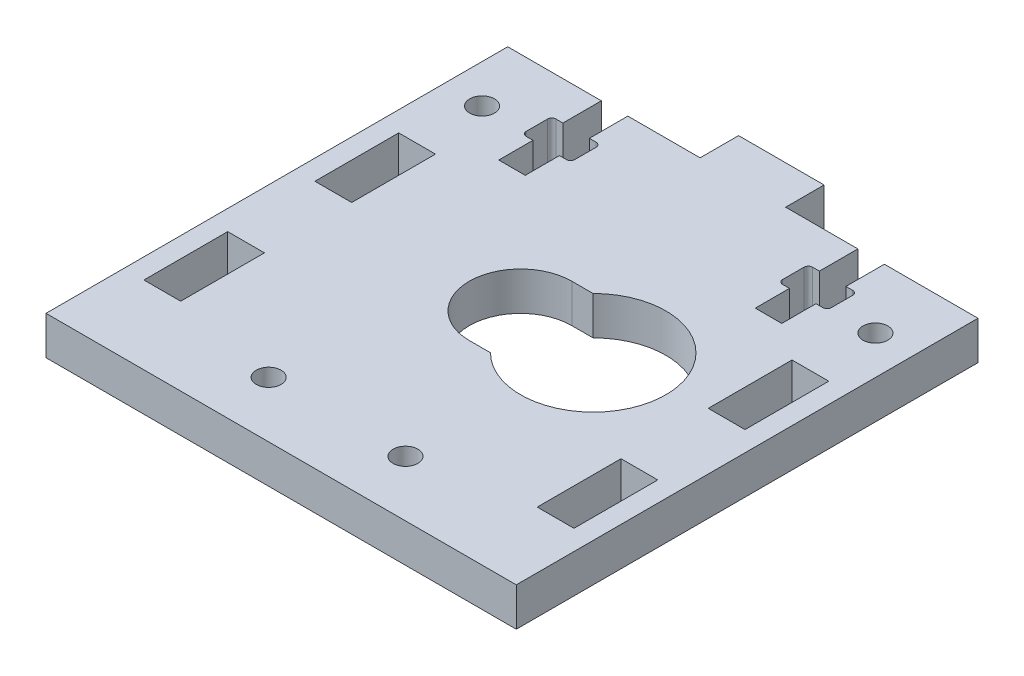
SolidWorks part; units mm, degrees
ref_plane "Front Plane" through (0, 0, 0) normal (0, 0, 1) x (1, 0, 0)
ref_plane "Top Plane" through (0, 0, 0) normal (0, 1, 0) x (1, 0, 0)
ref_plane "Right Plane" through (0, 0, 0) normal (1, 0, 0) x (0, 0, -1)
sketch "Sketch1" plane through (0, 0, 0) normal (0, 1, 0) x (1, 0, 0)
  line L1 (-27.5, 27) -> (27.5, 27)
  line L2 (-27.5, 27) -> (-27.5, -27)
  line L3 (-27.5, -27) -> (27.5, -27)
  line L4 (27.5, 27) -> (27.5, -27)
  line L5 (-27.5, 27) -> (27.5, -27) construction
  line L6 (-27.5, -27) -> (27.5, 27) construction
  point P0 (0, 0)
  dimension "D1" = 55
  dimension "D2" = 54
extrude "MainShape" add sketch "Sketch1" along normal blind 4.5
sketch "Sketch2" plane through (0, 4.5, 0) normal (0, 1, 0) x (1, 0, 0)
  line L0 (0, -27) -> (0, 27) construction
  line L1 (-27.5, -27) -> (27.5, -27) construction
  line L2 (27.5, 27) -> (-27.5, 27) construction
  line L4 (-5, 31.5) -> (5, 31.5)
  line L5 (-5, 31.5) -> (-5, 22.5)
  line L6 (-5, 22.5) -> (5, 22.5)
  line L7 (5, 31.5) -> (5, 22.5)
  line L8 (-5, 31.5) -> (5, 22.5) construction
  line L9 (-5, 22.5) -> (5, 31.5) construction
  dimension "D1" = 10
  dimension "D2" = 4.5
extrude "Tab1" add sketch "Sketch2" against normal through all
sketch "Sketch4" plane through (0, 4.5, 0) normal (0, 1, 0) x (1, 0, 0)
  line L0 (0, 31.5) -> (0, -27) construction
  line L1 (5, 31.5) -> (-5, 31.5) construction
  line L2 (-27.5, -27) -> (27.5, -27) construction
  line L3 (-15, 27) -> (-15, 15) construction
  line L4 (-5, 27) -> (-27.5, 27) construction
  line L5 (-13.45, 15) -> (-16.55, 15) construction
  line L6 (-16.55, 15) -> (-16.55, 27) construction
  line L7 (-13.45, 15) -> (-16.55, 15)
  line L8 (-16.55, 15) -> (-16.55, 19)
  line L9 (-16.55, 19) -> (-17.35, 19)
  line L10 (-17.85, 19.5) -> (-17.85, 22)
  line L11 (-17.35, 22.5) -> (-16.55, 22.5)
  line L12 (-16.55, 22.5) -> (-16.55, 27)
  line L13 (-16.55, 27) -> (-13.45, 27)
  line L14 (-13.45, 15) -> (-13.45, 27) construction
  line L15 (-13.45, 22.5) -> (-13.45, 27)
  line L16 (-12.65, 22.5) -> (-13.45, 22.5)
  line L17 (-12.15, 19.5) -> (-12.15, 22)
  line L18 (-13.45, 19) -> (-12.65, 19)
  line L19 (-13.45, 15) -> (-13.45, 19)
  line L20 (13.45, 15) -> (13.45, 27) construction
  line L21 (16.55, 15) -> (16.55, 27) construction
  line L22 (13.45, 15) -> (16.55, 15) construction
  line L23 (15, 27) -> (15, 15) construction
  line L24 (13.45, 15) -> (13.45, 19)
  line L25 (13.45, 19) -> (12.65, 19)
  line L26 (12.15, 19.5) -> (12.15, 22)
  line L27 (12.65, 22.5) -> (13.45, 22.5)
  line L28 (13.45, 22.5) -> (13.45, 27)
  line L29 (16.55, 27) -> (13.45, 27)
  line L30 (16.55, 22.5) -> (16.55, 27)
  line L31 (17.35, 22.5) -> (16.55, 22.5)
  line L32 (17.85, 19.5) -> (17.85, 22)
  line L33 (16.55, 19) -> (17.35, 19)
  line L34 (16.55, 15) -> (16.55, 19)
  line L35 (13.45, 15) -> (16.55, 15)
  arc A0 (-17.35, 19) -> (-17.85, 19.5) centre (-17.35, 19.5) cw
  arc A1 (-12.15, 19.5) -> (-12.65, 19) centre (-12.65, 19.5) cw
  arc A2 (-12.65, 22.5) -> (-12.15, 22) centre (-12.65, 22) cw
  arc A3 (-17.85, 22) -> (-17.35, 22.5) centre (-17.35, 22) cw
  arc A4 (17.85, 22) -> (17.35, 22.5) centre (17.35, 22) ccw
  arc A5 (12.65, 22.5) -> (12.15, 22) centre (12.65, 22) ccw
  arc A6 (12.15, 19.5) -> (12.65, 19) centre (12.65, 19.5) ccw
  arc A7 (17.35, 19) -> (17.85, 19.5) centre (17.35, 19.5) ccw
  point P24 (-17.85, 19)
  point P27 (-12.15, 19)
  point P30 (-12.15, 22.5)
  point P33 (-17.85, 22.5)
  point P56 (17.85, 22.5)
  point P57 (12.15, 22.5)
  point P58 (12.15, 19)
  point P59 (17.85, 19)
  dimension "D7" = 0.5
  dimension "D1" = 12
  dimension "D2" = 1.55
  dimension "D3" = 3.5
  dimension "D4" = 2.85
  dimension "D5" = 8
  dimension "D6" = 15
extrude "Cut-Extrude2" cut sketch "Sketch4" against normal through all
sketch "Sketch5" plane through (0, 4.5, 0) normal (0, 1, 0) x (1, 0, 0)
  line L0 (0, -27) -> (0, 31.5) construction
  line L1 (-27.5, -27) -> (27.5, -27) construction
  line L2 (5, 31.5) -> (-5, 31.5) construction
  line L3 (23, 27) -> (23, -27) construction
  line L4 (27.5, 27) -> (16.55, 27) construction
  line L5 (-23, 27) -> (-23, -27) construction
  line L6 (20.85, 11.9) -> (25.15, 11.9)
  line L7 (20.85, 11.9) -> (20.85, 2.1)
  line L8 (20.85, 2.1) -> (25.15, 2.1)
  line L9 (25.15, 11.9) -> (25.15, 2.1)
  line L10 (20.85, 11.9) -> (25.15, 2.1) construction
  line L11 (20.85, 2.1) -> (25.15, 11.9) construction
  line L12 (-20.85, 2.1) -> (-25.15, 11.9) construction
  line L13 (-20.85, 11.9) -> (-25.15, 2.1) construction
  line L14 (-25.15, 11.9) -> (-25.15, 2.1)
  line L15 (-20.85, 2.1) -> (-25.15, 2.1)
  line L16 (-20.85, 11.9) -> (-20.85, 2.1)
  line L17 (-20.85, 11.9) -> (-25.15, 11.9)
  line L18 (-27.5, -3) -> (27.5, -3) construction
  line L19 (-27.5, 27) -> (-27.5, -27) construction
  line L20 (27.5, -27) -> (27.5, 27) construction
  line L21 (-20.85, -17.9) -> (-25.15, -8.1) construction
  line L22 (-20.85, -8.1) -> (-25.15, -17.9) construction
  line L23 (20.85, -8.1) -> (25.15, -17.9) construction
  line L24 (20.85, -17.9) -> (25.15, -8.1) construction
  line L25 (-20.85, -17.9) -> (-25.15, -17.9)
  line L26 (-20.85, -17.9) -> (-20.85, -8.1)
  line L27 (-20.85, -8.1) -> (-25.15, -8.1)
  line L28 (-25.15, -17.9) -> (-25.15, -8.1)
  line L29 (25.15, -17.9) -> (25.15, -8.1)
  line L30 (20.85, -8.1) -> (25.15, -8.1)
  line L31 (20.85, -17.9) -> (20.85, -8.1)
  line L32 (20.85, -17.9) -> (25.15, -17.9)
  line L33 (-20.85, 11.9) -> (-25.15, 2.1) construction
  point P10 (23, 7)
  point P21 (-23, 7)
  point P36 (-23, -13)
  point P37 (23, -13)
  dimension "D1" = 23
  dimension "D2" = 9.8
  dimension "D3" = 4.3
  dimension "D4" = 20
  dimension "D5" = 20
extrude "Cut-Extrude3" cut sketch "Sketch5" against normal through all
sketch "Sketch6" plane through (0, 4.5, 0) normal (0, 1, 0) x (1, 0, 0)
  line L0 (0, -27) -> (0, 27) construction
  line L1 (5, 31.5) -> (-5, 31.5) construction
  line L3 (-27.5, 1) -> (27.5, 1) construction
  line L4 (-27.5, 27) -> (-27.5, -27) construction
  line L5 (27.5, -27) -> (27.5, 27) construction
  line L6 (27.5, 27) -> (16.55, 27) construction
  line L7 (-27.5, -27) -> (27.5, -27) construction
  line L9 (-27.5, 27) -> (27.5, 27) construction
  circle A0 centre (0, 1) radius 12
  point P4 (0, 31.5)
  dimension "D1" = 24
  dimension "D2" = 26
extrude "Cut-Extrude4" cut sketch "Sketch6" against normal through all
sketch "Sketch7" plane through (0, 4.5, 0) normal (0, 1, 0) x (1, 0, 0)
  line L0 (0, 1) -> (0, -27) construction
  line L3 (-27.5, -27) -> (27.5, -27) construction
  line L4 (8, -20.46) -> (-8, -20.46) construction
  circle A1 centre (-8, -20.46) radius 1.45
  circle A2 centre (8, -20.46) radius 1.45
  point P8 (0, -20.46)
  dimension "D1" = 2.9
  dimension "D3" = 21.46
extrude "Cut-Extrude5" [suppressed] cut sketch "Sketch7" against normal through all
sketch "Sketch8" plane through (0, 4.5, 0) normal (0, 1, 0) x (1, 0, 0)
  line L0 (-12, 1) -> (12, 1) construction
  line L1 (0, 1) -> (0, -20.46) construction
  line L2 (8, -20.46) -> (-8, -20.46) construction
  line L3 (0, -11) -> (0, 13) construction
  circle A0 centre (-8, -20.46) radius 1.45
  circle A1 centre (0, 1) radius 12 construction
  circle A2 centre (8, -20.46) radius 1.45
  dimension "D3" = 2.9
  dimension "D1" = 90
  dimension "D4" = 21.46
extrude "Cut-Extrude6" cut sketch "Sketch8" against normal through all
sketch "Sketch9" plane through (0, 4.5, 0) normal (0, 1, 0) x (1, 0, 0)
  line L0 (0, -27) -> (0, 31.5) construction
  line L1 (-27.5, -27) -> (27.5, -27) construction
  line L2 (5, 31.5) -> (-5, 31.5) construction
  line L3 (16, -27) -> (16, -16) construction
  line L4 (14.45, -16) -> (17.55, -16) construction
  line L5 (17.55, -16) -> (17.55, -27) construction
  line L6 (17.55, -27) -> (17.55, -22.5)
  line L7 (17.55, -22.5) -> (18.35, -22.5)
  line L8 (18.85, -22) -> (18.85, -19.5)
  line L9 (18.35, -19) -> (17.55, -19)
  line L10 (17.55, -19) -> (17.55, -16)
  line L11 (17.55, -16) -> (14.45, -16)
  line L12 (17.55, -27) -> (14.45, -27)
  line L13 (14.45, -16) -> (14.45, -27) construction
  line L14 (14.45, -19) -> (14.45, -16)
  line L15 (13.65, -19) -> (14.45, -19)
  line L16 (13.15, -22) -> (13.15, -19.5)
  line L17 (14.45, -22.5) -> (13.65, -22.5)
  line L18 (14.45, -27) -> (14.45, -22.5)
  line L19 (-14.45, -16) -> (-14.45, -27) construction
  line L20 (-17.55, -16) -> (-17.55, -27) construction
  line L21 (-14.45, -16) -> (-17.55, -16) construction
  line L22 (-16, -27) -> (-16, -16) construction
  line L23 (-14.45, -27) -> (-14.45, -22.5)
  line L24 (-14.45, -22.5) -> (-13.65, -22.5)
  line L25 (-13.15, -22) -> (-13.15, -19.5)
  line L26 (-13.65, -19) -> (-14.45, -19)
  line L27 (-14.45, -19) -> (-14.45, -16)
  line L28 (-17.55, -27) -> (-14.45, -27)
  line L29 (-17.55, -16) -> (-14.45, -16)
  line L30 (-17.55, -19) -> (-17.55, -16)
  line L31 (-18.35, -19) -> (-17.55, -19)
  line L32 (-18.85, -22) -> (-18.85, -19.5)
  line L33 (-17.55, -22.5) -> (-18.35, -22.5)
  line L34 (-17.55, -27) -> (-17.55, -22.5)
  arc A0 (18.35, -22.5) -> (18.85, -22) centre (18.35, -22) ccw
  arc A1 (18.85, -19.5) -> (18.35, -19) centre (18.35, -19.5) ccw
  arc A2 (13.15, -19.5) -> (13.65, -19) centre (13.65, -19.5) cw
  arc A3 (13.65, -22.5) -> (13.15, -22) centre (13.65, -22) cw
  arc A4 (-13.65, -22.5) -> (-13.15, -22) centre (-13.65, -22) ccw
  arc A5 (-13.15, -19.5) -> (-13.65, -19) centre (-13.65, -19.5) ccw
  arc A6 (-18.85, -19.5) -> (-18.35, -19) centre (-18.35, -19.5) cw
  arc A7 (-18.35, -22.5) -> (-18.85, -22) centre (-18.35, -22) cw
  point P16 (18.85, -22.5)
  point P19 (18.85, -19)
  point P30 (13.15, -19)
  point P31 (13.15, -22.5)
  point P54 (-13.15, -22.5)
  point P55 (-13.15, -19)
  point P56 (-18.85, -19)
  point P57 (-18.85, -22.5)
  dimension "D7" = 0.5
  dimension "D2" = 1.55
  dimension "D1" = 11
  dimension "D3" = 8
  dimension "D4" = 3.5
  dimension "D5" = 2.85
  dimension "D6" = 16
extrude "Cut-Extrude7" [suppressed] cut sketch "Sketch9" against normal through all
sketch "Sketch10" [suppressed] plane through (0, 0, 27) normal (0, 0, 1) x (1, 0, 0)
  line L0 (-27.5, 2.25) -> (27.5, 2.25) construction
  line L1 (-27.5, 4.5) -> (-27.5, 0) construction
  line L2 (27.5, 4.5) -> (27.5, 0) construction
  line L3 (-16, 4.5) -> (-16, 0) construction
  line L4 (-14.25, 4.5) -> (-17.75, 4.5) construction
  line L5 (16, 4.5) -> (16, 0) construction
  line L6 (17.75, 4.5) -> (14.25, 4.5) construction
  line L7 (17.75, 0) -> (14.25, 0) construction
  line L8 (-14.25, 0) -> (-17.75, 0) construction
  circle A0 centre (-16, 2.25) radius 1.6
  circle A1 centre (16, 2.25) radius 1.6
  dimension "D1" = 3.2
  dimension "D2" = 3.2
sketch "Sketch11" plane through (0, 4.5, 0) normal (0, 1, 0) x (1, 0, 0)
  line L0 (-20.85, 7) -> (-25.15, 7) construction
  line L1 (-20.85, 2.1) -> (-20.85, 11.9) construction
  line L2 (-25.15, 11.9) -> (-25.15, 2.1) construction
  line L3 (-23, 7) -> (-23, 27) construction
  line L4 (-16.55, 27) -> (-27.5, 27) construction
  line L5 (0, 31.5) -> (0, 0) construction
  line L6 (5, 31.5) -> (-5, 31.5) construction
  line L7 (23, 7) -> (23, 27) construction
  line L8 (20.85, 7) -> (25.15, 7) construction
  line L9 (-23, 7) -> (-23, 27) construction
  circle A0 centre (-23, 19.5) radius 1.45
  circle A1 centre (23, 19.5) radius 1.45
  dimension "D1" = 2.9
  dimension "D2" = 7.5
extrude "Cut-Extrude8" cut sketch "Sketch11" against normal through all
sketch "Sketch12" [suppressed] plane through (0, 4.5, 0) normal (0, 1, 0) x (1, 0, 0)
  line L0 (-27.5, -7) -> (-34, -17)
  line L1 (-27.5, 27) -> (-27.5, -27) construction
  line L2 (-34, -17) -> (-34, -27)
  line L3 (-34, -27) -> (-27.5, -27)
  line L4 (-27.5, -27) -> (-27.5, -7)
  line L5 (-27.5, -27) -> (27.5, -27) construction
  line L6 (0, -27) -> (0, 31.5) construction
  line L7 (5, 31.5) -> (-5, 31.5) construction
  line L8 (27.5, -27) -> (27.5, -7)
  line L9 (34, -27) -> (27.5, -27)
  line L10 (34, -17) -> (34, -27)
  line L11 (27.5, -7) -> (34, -17)
  point P4 (0, -27)
  dimension "D1" = 34
  dimension "D2" = 10
  dimension "D3" = 20
extrude "Boss-Extrude1" [suppressed] add sketch "Sketch12" against normal through all
sketch "Sketch14" [suppressed] plane through (0, 4.5, 0) normal (0, 1, 0) x (1, 0, 0)
  line L0 (-34, -27) -> (34, -27) construction
  line L2 (-34, -27) -> (34, -27) construction
  line L3 (0, -27) -> (0, 31.5) construction
  line L4 (5, 31.5) -> (-5, 31.5) construction
  line L6 (26.25, -16.5) -> (26.25, -27) construction
  line L8 (-28, -27) -> (-28, -16.5) construction
  line L9 (-26.25, -16.5) -> (-29.75, -16.5) construction
  line L10 (-29.75, -16.5) -> (-29.75, -27) construction
  line L11 (-26.25, -27) -> (-29.75, -27)
  line L12 (-29.75, -27) -> (-29.75, -23.2)
  line L13 (-29.75, -23.2) -> (-30.75, -23.2)
  line L14 (-31, -22.95) -> (-31, -19.25)
  line L15 (-30.75, -19) -> (-29.75, -19)
  line L16 (-29.75, -19) -> (-29.75, -16.5)
  line L17 (-29.75, -16.5) -> (-26.25, -16.5)
  line L18 (-26.25, -16.5) -> (-26.25, -27) construction
  line L19 (-26.25, -19) -> (-26.25, -16.5)
  line L20 (-25.25, -19) -> (-26.25, -19)
  line L21 (-25, -22.95) -> (-25, -19.25)
  line L22 (-26.25, -23.2) -> (-25.25, -23.2)
  line L23 (-26.25, -27) -> (-26.25, -23.2)
  line L24 (29.75, -16.5) -> (29.75, -27) construction
  line L25 (26.25, -16.5) -> (29.75, -16.5) construction
  line L26 (28, -27) -> (28, -16.5) construction
  line L27 (26.25, -27) -> (26.25, -23.2)
  line L28 (26.25, -23.2) -> (25.25, -23.2)
  line L29 (25, -22.95) -> (25, -19.25)
  line L30 (25.25, -19) -> (26.25, -19)
  line L31 (26.25, -19) -> (26.25, -16.5)
  line L32 (29.75, -16.5) -> (26.25, -16.5)
  line L33 (29.75, -19) -> (29.75, -16.5)
  line L34 (30.75, -19) -> (29.75, -19)
  line L35 (31, -22.95) -> (31, -19.25)
  line L36 (29.75, -23.2) -> (30.75, -23.2)
  line L37 (29.75, -27) -> (29.75, -23.2)
  line L38 (26.25, -27) -> (29.75, -27)
  line L39 (-26.25, -16.5) -> (-26.25, -27) construction
  arc A0 (-30.75, -23.2) -> (-31, -22.95) centre (-30.75, -22.95) cw
  arc A1 (-31, -19.25) -> (-30.75, -19) centre (-30.75, -19.25) cw
  arc A2 (-25, -19.25) -> (-25.25, -19) centre (-25.25, -19.25) ccw
  arc A3 (-25.25, -23.2) -> (-25, -22.95) centre (-25.25, -22.95) ccw
  arc A4 (25.25, -23.2) -> (25, -22.95) centre (25.25, -22.95) cw
  arc A5 (25, -19.25) -> (25.25, -19) centre (25.25, -19.25) cw
  arc A6 (31, -19.25) -> (30.75, -19) centre (30.75, -19.25) ccw
  arc A7 (30.75, -23.2) -> (31, -22.95) centre (30.75, -22.95) ccw
  point P2 (0, -27)
  dimension "D10" = 0.5
  dimension "D4" = 1.55
  dimension "D6" = 11
  dimension "D2" = 28
  dimension "D3" = 2.85
  dimension "D5" = 3.5
  dimension "D7" = 8
extrude "Cut-Extrude9" [suppressed] cut sketch "Sketch14" against normal through all
sketch "Sketch15" plane through (0, 4.5, 0) normal (0, 1, 0) x (1, 0, 0)
  circle A0 centre (0, 1) radius 12
  circle A1 centre (0, 1) radius 6
  circle A2 centre (0, 1) radius 12 construction
  dimension "D1" = 12
extrude "Boss-Extrude2" add sketch "Sketch15" against normal through all
sketch "Sketch16" plane through (0, 4.5, 0) normal (0, 1, 0) x (1, 0, 0)
  line L0 (0, 1) -> (27.5, 1) construction
  line L1 (27.5, -27) -> (27.5, 27) construction
  line L2 (0, 7) -> (2.4792, 7)
  line L3 (0, -5) -> (2.4792, -5)
  line L4 (0, 7) -> (0, -5)
  arc A0 (2.4792, -5) -> (2.4792, 7) centre (8.5, 1) ccw
  circle A1 centre (0, 1) radius 6 construction
  dimension "D1" = 17
  dimension "D2" = 8.5
extrude "Cut-Extrude10" cut sketch "Sketch16" against normal through all
equation "\"X-ROD-SPACING\"=45"
equation "\"Y-ROD-SPACING\"=75"
equation "\"Z-ROD-SPACING\"=17.5"
equation "\"Y-BED-OFFSET\"=2"
equation "\"Y-BED-ROD-INSET\"=3.5"
equation "\"Y-BED-SCREW-SPACING\"=209"
equation "\"Y-BED-SCREW-CUTOUT-SLOT-HEIGHT\"=2"
equation "\"T-SLOT-NUT-FILLET-RADIUS\"=0.5"
equation "\"T-SLOT-SCREW-SHAFT-RADIUS\"=1.55"
equation "\"T-SLOT-SCREW-SHAFT-CUTOUT-LENGTH\"=11.0"
equation "\"T-SLOT-NUT-DEPTH\"=3.5"
equation "\"T-SLOT-NUT-WIDTH\"=2.85"
equation "\"T-SLOT-NUT-END-DISTANCE\"=8"
equation "\"ACRYLIC-THICKNESS\"=10"
equation "\"ACRYLIC-THICKNESS2\"=4.5"
equation "\"ACRYLIC-TAB-CUTOUT-SIZE\"=\"ACRYLIC-THICKNESS\"+\"ACRYLIC-TAB-TOLERANCE\"*2"
equation "\"ACRYLIC-TAB-WIDTH\"=\"ACRYLIC-THICKNESS\""
equation "\"ACRYLIC-M3-HOLE\"=2.9"
equation "\"SMOOTHROD-CAP-SCREW-DISTANCE\"=20"
equation "\"FRAME-WIDTH-INNER\"=370"
equation "\"NEMA17-HOLE-SPACING\"=31"
equation "\"NEMA17-CENTRAL-CUTOUT\"=22.5"
equation "\"Z-BRACKET-REACH\"=55"
equation "\"Z-ROD-INSET\"=16"
equation "\"TOP-BRACKET-SPACING\"=40"
equation "\"SMOOTHROD-X-LENGTH\"=350"
equation "\"SMOOTHROD-Y-LENGTH\"=350"
equation "\"SMOOTHROD-Z-LENGTH\"=350"
equation "\"SMOOTHROD-TIGHTENING-HEADROOM\"=.25"
equation "\"LEADSCREW-Z-LENGTH\"=300"
equation "\"SCREW-LENGTH-FRAME\"=\"ACRYLIC-THICKNESS\" + 10"
equation "\"SCREW-LENGTH-MOTOR\"=\"ACRYLIC-THICKNESS\" + 5"
equation "\"SCREW-LENGTH-EXTRUDER\"=28"
equation "\"SCREW-HEAD-RADIUS\"=6"
equation "\"PRINTED-X-SMOOTHROD-DIAMETER\"=9.0"
equation "\"PRINTED-X-SMOOTHROD-CUTOUT\"=10"
equation "\"PRINTED-X-BASE-HEIGHT\"=10"
equation "\"PRINTED-LM8UU-CUTOUT-SIZE\"=15.5"
equation "\"PRINTED-LM8UU-CUTOUT-LENGTH\"=24.5"
equation "\"PRINTED-X-IDLER-HEIGHT\"=16"
equation "\"PSU-MOUNTING-WIDTH\"=95"
equation "\"PSU-MOUNTING-HEIGHT\"=177"
equation "\"Y-BELT-TO-ROD-DISTANCE\"=20"
equation "\"SPOOL-HOLDER-ROD-SPACING\"=150"
equation "\"ACRYLIC-X-CARRIAGE-WIDTH\"=55"
equation "\"ACRYLIC-X-CARRIAGE-HEIGHT\"=75"
equation "\"ACRYLIC-X-CARRIAGE-SCREW-SPACING-X\"=15"
equation "\"ACRYLIC-X-CARRIAGE-SCREW-SPACING-Y\"=33"
equation "\"ACRYLIC-X-CARRIAGE-CENTER-TAB-SPACING\"=14"
equation "\"D1@Sketch1\"=\"ACRYLIC-X-CARRIAGE-WIDTH\""
equation "\"D1@MainShape\" = \"ACRYLIC-THICKNESS2\""
equation "\"D1@Sketch2\"=\"ACRYLIC-TAB-WIDTH\""
equation "\"D2@Sketch2\"=\"ACRYLIC-THICKNESS2\""
equation "\"D1@Sketch4\"=\"T-SLOT-SCREW-SHAFT-CUTOUT-LENGTH\"+1"
equation "\"D2@Sketch4\"=\"T-SLOT-SCREW-SHAFT-RADIUS\""
equation "\"D3@Sketch4\"=\"T-SLOT-NUT-DEPTH\""
equation "\"D4@Sketch4\"=\"T-SLOT-NUT-WIDTH\""
equation "\"D5@Sketch4\"=\"T-SLOT-NUT-END-DISTANCE\""
equation "\"D6@Sketch4\"=\"ACRYLIC-X-CARRIAGE-SCREW-SPACING-X\""
equation "\"D7@Sketch4\"=\"T-SLOT-NUT-FILLET-RADIUS\""
equation "\"ACRYLIC-X-CARRIAGE-EXTRUDER-SHELF-DEPTH\"=\"ACRYLIC-X-CARRIAGE-EXTRUDER-OFFSET\" + 28"
equation "\"D2@Sketch1\"=\"ACRYLIC-X-CARRIAGE-EXTRUDER-SHELF-DEPTH\""
equation "\"ACRYLIC-X-CARRIAGE-LM8UU-CUTOUT-WIDTH\"=24.25"
equation "\"ACRYLIC-X-CARRIAGE-EXTRUDER-BRACE-SPACING\"=23"
equation "\"ACRYLIC-X-CARRIAGE-EXTRUDER-BRACE-TAB-OFFSET\"=20"
equation "\"ACRYLIC-X-CARRIAGE-EXTRUDER-BRACE-HEIGHT\"=35"
equation "\"ACRYLIC-X-CARRIAGE-EXTRUDER-BRACE-SCREW-SPACING\"=22"
equation "\"D1@Sketch5\"=\"ACRYLIC-X-CARRIAGE-EXTRUDER-BRACE-SPACING\""
equation "\"D2@Sketch5\"=\"ACRYLIC-TAB-WIDTH\"-\"KERF\"*2"
equation "\"D3@Sketch5\"=\"ACRYLIC-THICKNESS2\"-\"KERF\"*2"
equation "\"D4@Sketch5\"=\"ACRYLIC-X-CARRIAGE-EXTRUDER-BRACE-TAB-OFFSET\""
equation "\"D1@Sketch7\"=\"ACRYLIC-M3-HOLE\""
equation "\"D3@Sketch8\"=\"ACRYLIC-M3-HOLE\""
equation "\"ACRYLIC-X-CARRIAGE-EXTRUDER-ANGLE\"=90"
equation "\"D1@Sketch8\"=\"ACRYLIC-X-CARRIAGE-EXTRUDER-ANGLE\""
equation "\"ACRYLIC-X-CARRIAGE-EXTRUDER-OFFSET\"=26"
equation "\"D2@Sketch6\"=\"ACRYLIC-X-CARRIAGE-EXTRUDER-OFFSET\""
equation "\"D1@Sketch9\"=\"T-SLOT-SCREW-SHAFT-CUTOUT-LENGTH\""
equation "\"D2@Sketch9\"=\"T-SLOT-SCREW-SHAFT-RADIUS\""
equation "\"D3@Sketch9\"=\"T-SLOT-NUT-END-DISTANCE\""
equation "\"D4@Sketch9\"=\"T-SLOT-NUT-DEPTH\""
equation "\"D5@Sketch9\"=\"T-SLOT-NUT-WIDTH\""
equation "\"D7@Sketch9\"=\"T-SLOT-NUT-FILLET-RADIUS\""
equation "\"ACRYLIC-TAB-TOLERANCE\"=-.05"
equation "\"D1@Sketch11\"=\"ACRYLIC-M3-HOLE\""
equation "\"D6@Sketch14\"=\"T-SLOT-SCREW-SHAFT-CUTOUT-LENGTH\""
equation "\"D3@Sketch14\"=\"T-SLOT-NUT-WIDTH\""
equation "\"D5@Sketch14\"=\"T-SLOT-NUT-DEPTH\""
equation "\"D4@Sketch14\"=\"T-SLOT-SCREW-SHAFT-RADIUS\""
equation "\"D10@Sketch14\"=\"T-SLOT-NUT-FILLET-RADIUS\""
equation "\"D7@Sketch14\"=\"T-SLOT-NUT-END-DISTANCE\""
equation "\"KERF\"=0.1"
equation "\"PRINTED-M3-HOLE\"=3.5"
equation "\"PRINTED-M3-NUT-AF\"=6.25"
equation "\"ACRYLIC-X-CARRIAGE-LM8UU-CUTOUT-HEIGHT\"=11.0"
equation "\"ACRYLIC-X-CARRIAGE-DUAL-WIDTH-MULTIPLIER\"=1.65"
equation "\"ACRYLIC-X-CARRIAGE-DUAL-HOTEND-SPACING\"=42"
equation "\"ACRYLIC-X-CARRIAGE-DUAL-WIDTH\"=75"
equation "\"ACRYLIC-X-CARRIAGE-DUAL-FAN-OFFSET\"=52"
equation "\"ACRYLIC-X-CARRIAGE-DUAL-FAN-HEIGHT\"=20"
equation "\"ACRYLIC-X-CARRIAGE-DUAL-HOTEND-SEPARATION\"=36"
equation "\"ACRYLIC-X-CARRIAGE-DUAL-MOUNT-PLATE-DEPTH\"=75"
equation "\"ACRYLIC-X-CARRIAGE-DUAL-MOUNT-BRACE-WIDTH\"=33"
equation "\"ACRYLIC-X-CARRIAGE-DUAL-MOUNT-SCREW-WIDTH\"=40"
equation "\"BLOWER-FAN-WIDTH\"=15"
